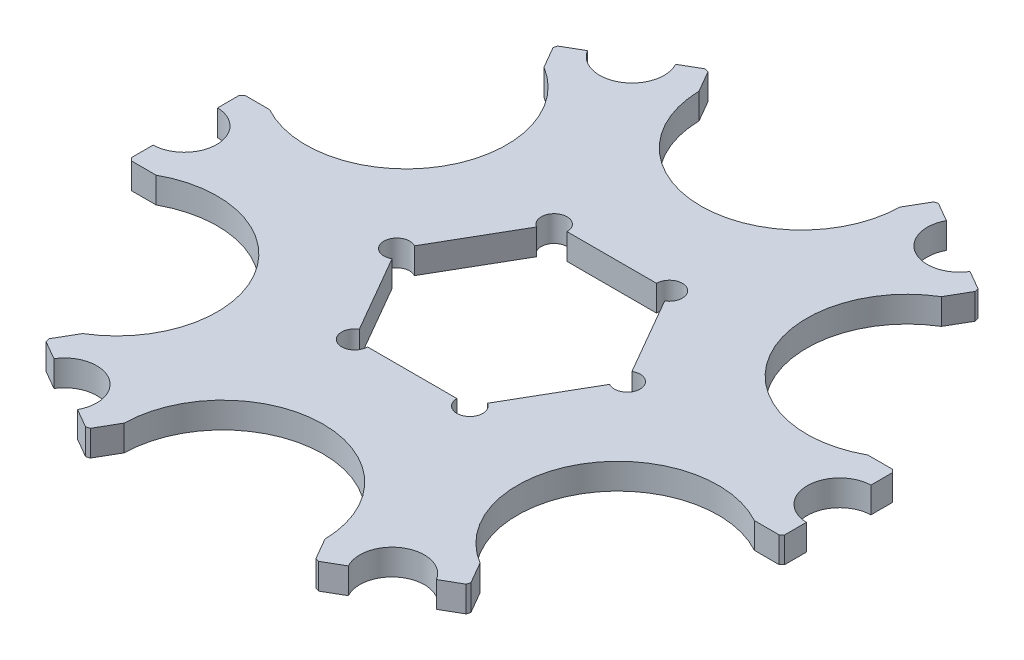
SolidWorks part; units mm, degrees
material "6061-T6 (SS)"
ref_plane "Front Plane" through (0, 0, 0) normal (0, 0, 1) x (1, 0, 0)
ref_plane "Top Plane" through (0, 0, 0) normal (0, 1, 0) x (1, 0, 0)
ref_plane "Right Plane" through (0, 0, 0) normal (1, 0, 0) x (0, 0, -1)
sketch "Sketch1" plane through (0, 0, 0) normal (0, 1, 0) x (1, 0, 0)
  line L0 (0, 0) -> (-62.5623, 0) construction
  line L1 (10.6246, 18.4023) -> (-10.6246, 18.4023)
  line L2 (-10.6246, 18.4023) -> (-21.2491, 0)
  line L3 (-21.2491, 0) -> (-10.6246, -18.4023)
  line L4 (-10.6246, -18.4023) -> (10.6246, -18.4023)
  line L5 (10.6246, -18.4023) -> (21.2491, 0)
  line L6 (21.2491, 0) -> (10.6246, 18.4023)
  line L7 (-60.2361, 10.4648) -> (-60.2361, 5.9505)
  line L8 (-60.4139, 0) -> (-60.4139, -29.149) construction
  line L9 (-60.2361, -5.9505) -> (-60.2361, -10.4648)
  line L10 (-35.2713, 49.1908) -> (-39.1808, 46.9336)
  line L11 (-21.0553, 57.3984) -> (-24.9648, 55.1412)
  line L12 (24.9648, 55.1412) -> (21.0553, 57.3984)
  line L13 (39.1808, 46.9336) -> (35.2713, 49.1908)
  line L14 (60.2361, 5.9505) -> (60.2361, 10.4648)
  line L15 (60.2361, -10.4648) -> (60.2361, -5.9505)
  line L16 (35.2713, -49.1908) -> (39.1808, -46.9336)
  line L17 (21.0553, -57.3984) -> (24.9648, -55.1412)
  line L18 (-24.9648, -55.1412) -> (-21.0553, -57.3984)
  line L19 (-39.1808, -46.9336) -> (-35.2713, -49.1908)
  line L20 (-60.2361, 10.4648) -> (-55.1561, 10.4648)
  line L21 (-39.1808, 46.9336) -> (-36.6408, 42.5342)
  line L22 (-21.0553, 57.3984) -> (-18.5153, 52.999)
  line L23 (21.0553, 57.3984) -> (18.5153, 52.999)
  line L24 (39.1808, 46.9336) -> (36.6408, 42.5342)
  line L25 (60.2361, 10.4648) -> (55.1561, 10.4648)
  line L26 (60.2361, -10.4648) -> (55.1561, -10.4648)
  line L27 (39.1808, -46.9336) -> (36.6408, -42.5342)
  line L28 (21.0553, -57.3984) -> (18.5153, -52.999)
  line L29 (-21.0553, -57.3984) -> (-18.5153, -52.999)
  line L30 (-39.1808, -46.9336) -> (-36.6408, -42.5342)
  line L31 (-60.2361, -10.4648) -> (-55.1561, -10.4648)
  line L32 (21.0553, 57.3984) -> (18.5153, 52.999)
  line L33 (-21.0553, 57.3984) -> (-18.5153, 52.999)
  line L34 (60.2361, 10.4648) -> (55.1561, 10.4648)
  line L35 (39.1808, 46.9336) -> (36.6408, 42.5342)
  line L36 (39.1808, -46.9336) -> (36.6408, -42.5342)
  line L37 (60.2361, -10.4648) -> (55.1561, -10.4648)
  line L38 (-21.0553, -57.3984) -> (-18.5153, -52.999)
  line L39 (21.0553, -57.3984) -> (18.5153, -52.999)
  line L40 (-60.2361, -10.4648) -> (-55.1561, -10.4648)
  line L41 (-39.1808, -46.9336) -> (-36.6408, -42.5342)
  circle A0 centre (0, 0) radius 18.4023 construction
  circle A1 centre (-21.2491, 0) radius 2.3813
  arc A2 (-60.4139, 5.9531) -> (-60.4139, -5.9531) centre (-60.4139, 0) ccw construction
  circle A3 centre (-10.6246, 18.4023) radius 2.3813
  circle A4 centre (10.6246, 18.4023) radius 2.3813
  circle A5 centre (21.2491, 0) radius 2.3813
  circle A6 centre (10.6246, -18.4023) radius 2.3813
  circle A7 centre (-10.6246, -18.4023) radius 2.3813
  arc A8 (-60.2361, 5.9505) -> (-60.2361, -5.9505) centre (-60.4139, 0) cw
  arc A9 (-60.2361, -5.9505) -> (-60.2361, 5.9505) centre (-60.4139, 0) ccw construction
  arc A10 (-24.9648, 55.1412) -> (-35.2713, 49.1908) centre (-30.207, 52.32) cw
  arc A11 (35.2713, 49.1908) -> (24.9648, 55.1412) centre (30.2069, 52.32) cw
  arc A12 (60.2361, -5.9505) -> (60.2361, 5.9505) centre (60.4139, 0) cw
  arc A13 (24.9648, -55.1412) -> (35.2713, -49.1908) centre (30.207, -52.32) cw
  arc A14 (-35.2713, -49.1908) -> (-24.9648, -55.1412) centre (-30.2069, -52.32) cw
  arc A27 (-55.1561, 10.4648) -> (-36.6408, 42.5342) centre (-46.1938, 26.67) ccw
  arc A28 (-18.5153, 52.999) -> (18.5153, 52.999) centre (0, 53.34) ccw
  arc A29 (36.6408, 42.5342) -> (55.1561, 10.4648) centre (46.1938, 26.67) ccw
  arc A30 (55.1561, -10.4648) -> (36.6408, -42.5342) centre (46.1938, -26.67) ccw
  arc A31 (18.5153, -52.999) -> (-18.5153, -52.999) centre (0, -53.34) ccw
  arc A32 (-36.6408, -42.5342) -> (-55.1561, -10.4648) centre (-46.1938, -26.67) ccw
  point P27 (0, 0)
  point P58 (0, 0)
  point P74 (0, 0)
  point P87 (0, 0)
  point P98 (0, 0)
  dimension "D1" = 11.9062
  dimension "D4" = 4.7625
  dimension "D10" = 6
  dimension "D2" = 60.4139
  dimension "D3" = 36.8046
  dimension "D6" = 0.3556
  dimension "D7" = 20.9296
  dimension "D9" = 5.08
  dimension "D11" = 53.34
  dimension "D5" = 6
  dimension "D8" = 6
  dimension "D12" = 6
extrude "Boss-Extrude1" add sketch "Sketch1" along normal blind 4.7625 contours L18 L17 A13 L16 L15 A12 L14 L13 A11 L12 L11 A10 L10 L7 A8 L9 L19 A14 A7 L3 A1 L2 A3 L1 A4 L6 A5 L5 A6 L4 region at (-57.6961, 0, -8.8007)
chamfer "Chamfer1" distance 0.508 angle 45 12 edges at (-60.2361, 2.3813, 10.4648) (-39.1808, 2.3813, 46.9336) (-21.0553, 2.3813, 57.3984) (21.0553, 2.3813, 57.3984) (39.1808, 2.3813, 46.9336) (60.2361, 2.3813, 10.4648) (60.2361, 2.3813, -10.4648) (39.1808, 2.3813, -46.9336) (21.0553, 2.3813, -57.3984) (-21.0553, 2.3813, -57.3984) (-39.1808, 2.3813, -46.9336) (-60.2361, 2.3813, -10.4648)
sketch "Sketch3" plane through (0, 0, 0) normal (0, 0, 1) x (1, 0, 0)
  line L0 (0, 32.7405) -> (0, -26.7673) construction
